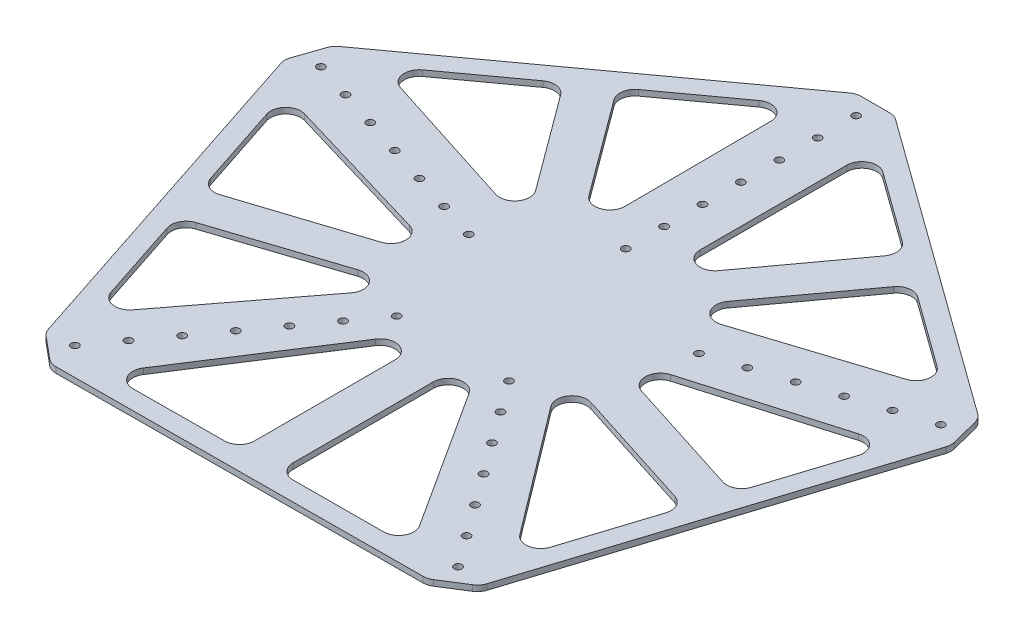
SolidWorks part; units mm, degrees
ref_plane "Front Plane" through (0, 0, 0) normal (0, 0, 1) x (1, 0, 0)
ref_plane "Top Plane" through (0, 0, 0) normal (0, 1, 0) x (1, 0, 0)
ref_plane "Right Plane" through (0, 0, 0) normal (1, 0, 0) x (0, 0, -1)
sketch "Sketch1" plane through (0, 0, 0) normal (0, 1, 0) x (1, 0, 0)
  line L0 (0, 0) -> (0, 50.8) construction
  line L1 (52.2614, 3.6272) -> (44.4123, 27.784)
  line L2 (12.7, 50.8244) -> (-12.7, 50.8244)
  line L3 (12.7, 50.8244) -> (12.7, 812.8244)
  line L4 (12.7, 812.8244) -> (-12.7, 812.8244)
  line L5 (-12.7, 50.8244) -> (-12.7, 812.8244)
  line L6 (52.2614, 3.6272) -> (776.9664, 239.0981)
  line L7 (776.9664, 239.0981) -> (769.1174, 263.255)
  line L8 (44.4123, 27.784) -> (769.1174, 263.255)
  line L9 (0, 0) -> (48.3137, 15.6981) construction
  line L10 (19.5993, -48.5827) -> (40.1483, -33.6529)
  line L11 (19.5993, -48.5827) -> (467.4917, -665.0536)
  line L12 (467.4917, -665.0536) -> (488.0407, -650.1239)
  line L13 (40.1483, -33.6529) -> (488.0407, -650.1239)
  line L14 (0, 0) -> (29.8595, -41.0981) construction
  line L15 (-40.1483, -33.6529) -> (-19.5993, -48.5827)
  line L16 (-40.1483, -33.6529) -> (-488.0407, -650.1239)
  line L17 (-488.0407, -650.1239) -> (-467.4917, -665.0536)
  line L18 (-19.5993, -48.5827) -> (-467.4917, -665.0536)
  line L19 (0, 0) -> (-29.8595, -41.0981) construction
  line L20 (-44.4123, 27.784) -> (-52.2614, 3.6272)
  line L21 (-44.4123, 27.784) -> (-769.1174, 263.255)
  line L22 (-769.1174, 263.255) -> (-776.9664, 239.0981)
  line L23 (-52.2614, 3.6272) -> (-776.9664, 239.0981)
  line L24 (0, 0) -> (-48.3137, 15.6981) construction
  circle A0 centre (0, 63.5244) radius 2.54
  circle A1 centre (0, 89.0462) radius 2.54
  circle A2 centre (0, 114.5681) radius 2.54
  circle A3 centre (0, 140.09) radius 2.54
  circle A4 centre (0, 165.6119) radius 2.54
  circle A5 centre (0, 191.1337) radius 2.54
  circle A6 centre (0, 216.6556) radius 2.54
  circle A7 centre (0, 242.1775) radius 2.54
  circle A8 centre (0, 267.6993) radius 2.54
  circle A9 centre (0, 293.2212) radius 2.54
  circle A10 centre (0, 318.7431) radius 2.54
  circle A11 centre (0, 344.2649) radius 2.54
  circle A12 centre (0, 369.7868) radius 2.54
  circle A13 centre (0, 395.3087) radius 2.54
  circle A14 centre (0, 420.8305) radius 2.54
  circle A15 centre (0, 446.3524) radius 2.54
  circle A16 centre (0, 471.8743) radius 2.54
  circle A17 centre (0, 497.3961) radius 2.54
  circle A18 centre (0, 522.918) radius 2.54
  circle A19 centre (0, 548.4399) radius 2.54
  circle A20 centre (0, 573.9618) radius 2.54
  circle A21 centre (0, 599.4836) radius 2.54
  circle A22 centre (0, 625.0055) radius 2.54
  circle A23 centre (0, 650.5274) radius 2.54
  circle A24 centre (0, 676.0492) radius 2.54
  circle A25 centre (0, 701.5711) radius 2.54
  circle A26 centre (0, 727.093) radius 2.54
  circle A27 centre (0, 752.6148) radius 2.54
  circle A28 centre (0, 778.1367) radius 2.54
  circle A29 centre (0, 803.6586) radius 2.54
  circle A30 centre (60.4153, 19.6301) radius 2.54
  circle A31 centre (84.688, 27.5168) radius 2.54
  circle A32 centre (108.9607, 35.4035) radius 2.54
  circle A33 centre (133.2335, 43.2902) radius 2.54
  circle A34 centre (157.5062, 51.1769) radius 2.54
  circle A35 centre (181.779, 59.0636) radius 2.54
  circle A36 centre (206.0517, 66.9503) radius 2.54
  circle A37 centre (230.3244, 74.837) radius 2.54
  circle A38 centre (254.5972, 82.7236) radius 2.54
  circle A39 centre (278.8699, 90.6103) radius 2.54
  circle A40 centre (303.1427, 98.497) radius 2.54
  circle A41 centre (327.4154, 106.3837) radius 2.54
  circle A42 centre (351.6881, 114.2704) radius 2.54
  circle A43 centre (375.9609, 122.1571) radius 2.54
  circle A44 centre (400.2336, 130.0438) radius 2.54
  circle A45 centre (424.5064, 137.9305) radius 2.54
  circle A46 centre (448.7791, 145.8172) radius 2.54
  circle A47 centre (473.0518, 153.7039) radius 2.54
  circle A48 centre (497.3246, 161.5906) radius 2.54
  circle A49 centre (521.5973, 169.4772) radius 2.54
  circle A50 centre (545.8701, 177.3639) radius 2.54
  circle A51 centre (570.1428, 185.2506) radius 2.54
  circle A52 centre (594.4155, 193.1373) radius 2.54
  circle A53 centre (618.6883, 201.024) radius 2.54
  circle A54 centre (642.961, 208.9107) radius 2.54
  circle A55 centre (667.2338, 216.7974) radius 2.54
  circle A56 centre (691.5065, 224.6841) radius 2.54
  circle A57 centre (715.7792, 232.5708) radius 2.54
  circle A58 centre (740.052, 240.4575) radius 2.54
  circle A59 centre (764.3247, 248.3442) radius 2.54
  circle A60 centre (37.3387, -51.3923) radius 2.54
  circle A61 centre (52.3401, -72.0399) radius 2.54
  circle A62 centre (67.3414, -92.6875) radius 2.54
  circle A63 centre (82.3428, -113.3352) radius 2.54
  circle A64 centre (97.3442, -133.9828) radius 2.54
  circle A65 centre (112.3456, -154.6304) radius 2.54
  circle A66 centre (127.347, -175.2781) radius 2.54
  circle A67 centre (142.3483, -195.9257) radius 2.54
  circle A68 centre (157.3497, -216.5733) radius 2.54
  circle A69 centre (172.3511, -237.2209) radius 2.54
  circle A70 centre (187.3525, -257.8686) radius 2.54
  circle A71 centre (202.3539, -278.5162) radius 2.54
  circle A72 centre (217.3552, -299.1638) radius 2.54
  circle A73 centre (232.3566, -319.8114) radius 2.54
  circle A74 centre (247.358, -340.4591) radius 2.54
  circle A75 centre (262.3594, -361.1067) radius 2.54
  circle A76 centre (277.3607, -381.7543) radius 2.54
  circle A77 centre (292.3621, -402.4019) radius 2.54
  circle A78 centre (307.3635, -423.0496) radius 2.54
  circle A79 centre (322.3649, -443.6972) radius 2.54
  circle A80 centre (337.3663, -464.3448) radius 2.54
  circle A81 centre (352.3676, -484.9924) radius 2.54
  circle A82 centre (367.369, -505.6401) radius 2.54
  circle A83 centre (382.3704, -526.2877) radius 2.54
  circle A84 centre (397.3718, -546.9353) radius 2.54
  circle A85 centre (412.3731, -567.5829) radius 2.54
  circle A86 centre (427.3745, -588.2306) radius 2.54
  circle A87 centre (442.3759, -608.8782) radius 2.54
  circle A88 centre (457.3773, -629.5258) radius 2.54
  circle A89 centre (472.3787, -650.1734) radius 2.54
  circle A90 centre (-37.3387, -51.3923) radius 2.54
  circle A91 centre (-52.3401, -72.0399) radius 2.54
  circle A92 centre (-67.3414, -92.6875) radius 2.54
  circle A93 centre (-82.3428, -113.3352) radius 2.54
  circle A94 centre (-97.3442, -133.9828) radius 2.54
  circle A95 centre (-112.3456, -154.6304) radius 2.54
  circle A96 centre (-127.347, -175.2781) radius 2.54
  circle A97 centre (-142.3483, -195.9257) radius 2.54
  circle A98 centre (-157.3497, -216.5733) radius 2.54
  circle A99 centre (-172.3511, -237.2209) radius 2.54
  circle A100 centre (-187.3525, -257.8686) radius 2.54
  circle A101 centre (-202.3539, -278.5162) radius 2.54
  circle A102 centre (-217.3552, -299.1638) radius 2.54
  circle A103 centre (-232.3566, -319.8114) radius 2.54
  circle A104 centre (-247.358, -340.4591) radius 2.54
  circle A105 centre (-262.3594, -361.1067) radius 2.54
  circle A106 centre (-277.3607, -381.7543) radius 2.54
  circle A107 centre (-292.3621, -402.4019) radius 2.54
  circle A108 centre (-307.3635, -423.0496) radius 2.54
  circle A109 centre (-322.3649, -443.6972) radius 2.54
  circle A110 centre (-337.3663, -464.3448) radius 2.54
  circle A111 centre (-352.3676, -484.9924) radius 2.54
  circle A112 centre (-367.369, -505.6401) radius 2.54
  circle A113 centre (-382.3704, -526.2877) radius 2.54
  circle A114 centre (-397.3718, -546.9353) radius 2.54
  circle A115 centre (-412.3731, -567.5829) radius 2.54
  circle A116 centre (-427.3745, -588.2306) radius 2.54
  circle A117 centre (-442.3759, -608.8782) radius 2.54
  circle A118 centre (-457.3773, -629.5258) radius 2.54
  circle A119 centre (-472.3787, -650.1734) radius 2.54
  circle A120 centre (-60.4153, 19.6301) radius 2.54
  circle A121 centre (-84.688, 27.5168) radius 2.54
  circle A122 centre (-108.9607, 35.4035) radius 2.54
  circle A123 centre (-133.2335, 43.2902) radius 2.54
  circle A124 centre (-157.5062, 51.1769) radius 2.54
  circle A125 centre (-181.779, 59.0636) radius 2.54
  circle A126 centre (-206.0517, 66.9503) radius 2.54
  circle A127 centre (-230.3244, 74.837) radius 2.54
  circle A128 centre (-254.5972, 82.7236) radius 2.54
  circle A129 centre (-278.8699, 90.6103) radius 2.54
  circle A130 centre (-303.1427, 98.497) radius 2.54
  circle A131 centre (-327.4154, 106.3837) radius 2.54
  circle A132 centre (-351.6881, 114.2704) radius 2.54
  circle A133 centre (-375.9609, 122.1571) radius 2.54
  circle A134 centre (-400.2336, 130.0438) radius 2.54
  circle A135 centre (-424.5064, 137.9305) radius 2.54
  circle A136 centre (-448.7791, 145.8172) radius 2.54
  circle A137 centre (-473.0518, 153.7039) radius 2.54
  circle A138 centre (-497.3246, 161.5906) radius 2.54
  circle A139 centre (-521.5973, 169.4772) radius 2.54
  circle A140 centre (-545.8701, 177.3639) radius 2.54
  circle A141 centre (-570.1428, 185.2506) radius 2.54
  circle A142 centre (-594.4155, 193.1373) radius 2.54
  circle A143 centre (-618.6883, 201.024) radius 2.54
  circle A144 centre (-642.961, 208.9107) radius 2.54
  circle A145 centre (-667.2338, 216.7974) radius 2.54
  circle A146 centre (-691.5065, 224.6841) radius 2.54
  circle A147 centre (-715.7792, 232.5708) radius 2.54
  circle A148 centre (-740.052, 240.4575) radius 2.54
  circle A149 centre (-764.3247, 248.3442) radius 2.54
  point P329 (0, 0)
  dimension "D5" = 5.08
  dimension "D6" = 12.7
  dimension "D7" = 12.7
  dimension "D1" = 50.8
  dimension "D2" = 762
  dimension "D3" = 25.4
  dimension "D4" = 12.7
  dimension "D8" = 30
  dimension "D9" = 5
sketch "Sketch2" plane through (0, 0, 0) normal (0, 1, 0) x (1, 0, 0)
  line L0 (-214.1133, 82.9232) -> (-222.3752, 58.9005)
  line L1 (-44.4123, 27.784) -> (-769.1174, 263.255) construction
  line L2 (-52.2614, 3.6272) -> (-776.9664, 239.0981) construction
  line L4 (-40.1483, -33.6529) -> (-488.0407, -650.1239) construction
  line L5 (-144.6422, -177.4764) -> (-125.0914, -193.78)
  line L6 (-19.5993, -48.5827) -> (-467.4917, -665.0536) construction
  line L8 (19.5993, -48.5827) -> (467.4917, -665.0536) construction
  line L9 (124.0932, -192.4062) -> (145.6404, -178.8503)
  line L10 (40.1483, -33.6529) -> (488.0407, -650.1239) construction
  line L12 (52.2614, 3.6272) -> (776.9664, 239.0981) construction
  line L13 (221.336, 58.5629) -> (215.1021, 83.2445)
  line L14 (44.4123, 27.784) -> (769.1174, 263.255) construction
  line L16 (12.7, 50.8244) -> (12.7, 812.8244) construction
  line L17 (12.7, 229.4775) -> (-12.7, 229.4775)
  line L18 (-12.7, 50.8244) -> (-12.7, 812.8244) construction
  line L19 (-214.1133, 82.9232) -> (-12.7, 229.4775)
  line L20 (12.7, 229.4775) -> (215.1021, 83.2445)
  line L21 (221.336, 58.5629) -> (145.6404, -178.8503)
  line L22 (124.0932, -192.4062) -> (-125.0914, -193.78)
  line L23 (-144.6422, -177.4764) -> (-222.3752, 58.9005)
  dimension "D1" = 12.7
  dimension "D2" = 12.7
  dimension "D3" = 12.7
  dimension "D4" = 12.7
  dimension "D5" = 12.7
extrude "Boss-Extrude1" add sketch "Sketch2" along normal blind 3.81 contours L0 L23 L5 L22 L9 L21 L13 L20 L17 L19
extrude "Cut-Extrude2" cut sketch "Sketch1" along normal blind 3.81 contours A32 | A31 | A63 | A64 | A66 | A126 | A125 | A124 | A123 | A122 | A121 | A120 | A6 | A5 | A4 | A3 | A2 | A1 | A0 | A36 | A35 | A34 | A33 | A60 | A61 | A62 | A65 | A96 | A95 | A94 | A93 | A92 | A91 | A90 region at (84.688, 0, -27.5168) region at (108.9607, 0, -35.4035) region at (82.3428, 0, 113.3352) region at (97.3442, 0, 133.9828) region at (127.347, 0, 175.2781)
sketch "Sketch4" plane through (0, 3.81, 0) normal (0, 1, 0) x (1, 0, 0)
  line L0 (12.7, 18.2286) -> (113.901, 156.361) construction
  line L1 (-183.5087, -59.288) -> (218.2191, 70.9037) construction
  line L2 (-12.7, 229.4775) -> (-10.3699, -193.1475) construction
  line L3 (124.0932, -192.4062) -> (-125.0914, -193.78) construction
  line L4 (-11.5349, 18.165) -> (-113.4067, 156.2003) construction
  line L5 (-214.1133, 82.9232) -> (-12.7, 229.4775) construction
  line L6 (-113.4067, 156.2003) -> (-214.1133, 82.9232) construction
  line L7 (-113.4067, 156.2003) -> (-12.7, 229.4775) construction
  line L11 (-45.0709, 42.2185) -> (-116.1346, 138.5093)
  line L12 (-116.1346, 138.5093) -> (-186.3856, 87.3926)
  line L13 (-186.3856, 87.3926) -> (-45.0709, 42.2185)
  line L18 (12.7, 229.4775) -> (215.1021, 83.2445) construction
  line L19 (-144.6422, -177.4764) -> (-222.3752, 58.9005) construction
  line L20 (12.7, 229.4775) -> (12.7, -193.0203) construction
  line L21 (221.336, 58.5629) -> (215.1021, 83.2445) construction
  line L25 (-25.2632, 204.6299) -> (-95.5957, 153.454)
  line L26 (-95.5957, 153.454) -> (-24.4495, 57.0515)
  line L27 (-24.4495, 57.0515) -> (-25.2632, 204.6299)
  line L34 (96.1006, 153.5537) -> (25.4, 204.634)
  line L35 (25.4, 204.634) -> (25.4, 57.0522)
  line L36 (25.4, 57.0522) -> (96.1006, 153.5537)
  line L40 (46.0696, 42.2867) -> (116.6898, 138.6783)
  line L41 (116.6898, 138.6783) -> (187.3099, 87.6562)
  line L42 (187.3099, 87.6562) -> (46.0696, 42.2867)
  line L47 (-54.3133, -4.0681) -> (-202.7403, 39.8469)
  line L48 (-202.7403, 39.8469) -> (-175.3946, -43.3081)
  line L49 (-175.3946, -43.3081) -> (-54.3133, -4.0681)
  line L53 (-46.3292, -27.5453) -> (-167.4769, -67.385)
  line L54 (-167.4769, -67.385) -> (-140.1155, -150.5877)
  line L55 (-140.1155, -150.5877) -> (-46.3292, -27.5453)
  line L56 (0, 229.4775) -> (0, -193.0203) construction
  line L57 (12.7, 229.4775) -> (-12.7, 229.4775) construction
  line L61 (-12.7, -43.0904) -> (-101.6849, -180.9376)
  line L62 (-101.6849, -180.9376) -> (-12.7, -180.3972)
  line L63 (-12.7, -180.3972) -> (-12.7, -43.0904)
  line L67 (12.7, -43.1229) -> (12.7, -180.2573)
  line L68 (12.7, -180.2573) -> (100.864, -179.821)
  line L69 (100.864, -179.821) -> (12.7, -43.1229)
  line L70 (-218.2443, 70.9119) -> (184.3475, -57.4485) construction
  line L71 (-214.1133, 82.9232) -> (-222.3752, 58.9005) construction
  line L72 (221.336, 58.5629) -> (145.6404, -178.8503) construction
  line L76 (46.9042, -26.9566) -> (140.9944, -151.6141)
  line L77 (140.9944, -151.6141) -> (168.3898, -65.6905)
  line L78 (168.3898, -65.6905) -> (46.9042, -26.9566)
  line L82 (56.0687, -3.2188) -> (201.9724, 39.6385)
  line L83 (201.9724, 39.6385) -> (176.1055, -41.4908)
  line L84 (176.1055, -41.4908) -> (56.0687, -3.2188)
extrude "Cut-Extrude4" cut sketch "Sketch4" against normal blind 25.4 contours L11 L12 L13
fillet "Fillet1" radius 10 3 edges at (-186.3856, 1.905, -87.3926) (-45.0709, 1.905, -42.2185) (-116.1346, 1.905, -138.5093)
extrude "Cut-Extrude5" cut sketch "Sketch4<3>" against normal blind 25.4 contours L47 L48 L49 | L25 L26 L27 | L11 L12 L13 | L34 L35 L36 | L40 L41 L42 | L82 L83 L84 | L76 L77 L78 | L67 L68 L69 | L61 L62 L63 | L53 L54 L55
sketch "Sketch4<3>" plane through (0, 3.81, 0) normal (0, 1, 0) x (1, 0, 0) same geometry as "Sketch4"
fillet "Fillet2" radius 10 30 edges at (96.1006, 1.905, -153.5537) (25.4, 1.905, -204.634) (25.4, 1.905, -57.0522) (116.6898, 1.905, -138.6783) (46.0696, 1.905, -42.2867) (187.3099, 1.905, -87.6562) (56.0687, 1.905, 3.2188) (176.1055, 1.905, 41.4908) (201.9724, 1.905, -39.6385) (46.9042, 1.905, 26.9566) (140.9944, 1.905, 151.6141) (168.3898, 1.905, 65.6905) (12.7, 1.905, 180.2573) (100.864, 1.905, 179.821) (12.7, 1.905, 43.1229) (-12.7, 1.905, 43.0904) (-101.6849, 1.905, 180.9376) (-12.7, 1.905, 180.3972) (-54.3133, 1.905, 4.0681) (-175.3946, 1.905, 43.3081) (-202.7403, 1.905, -39.8469) (-167.4769, 1.905, 67.385) (-140.1155, 1.905, 150.5877) (-46.3292, 1.905, 27.5453) (-24.4495, 1.905, -57.0515) (-25.2632, 1.905, -204.6299) (-95.5957, 1.905, -153.454) (-45.0709, 1.905, -42.2185) (-116.1346, 1.905, -138.5093) (-186.3856, 1.905, -87.3926)
fillet "Fillet3" radius 10 10 edges at (-12.7, 1.905, -229.4775) (12.7, 1.905, -229.4775) (215.1021, 1.905, -83.2445) (221.336, 1.905, -58.5629) (145.6404, 1.905, 178.8503) (124.0932, 1.905, 192.4062) (-125.0914, 1.905, 193.78) (-144.6422, 1.905, 177.4764) (-222.3752, 1.905, -58.9005) (-214.1133, 1.905, -82.9232)
